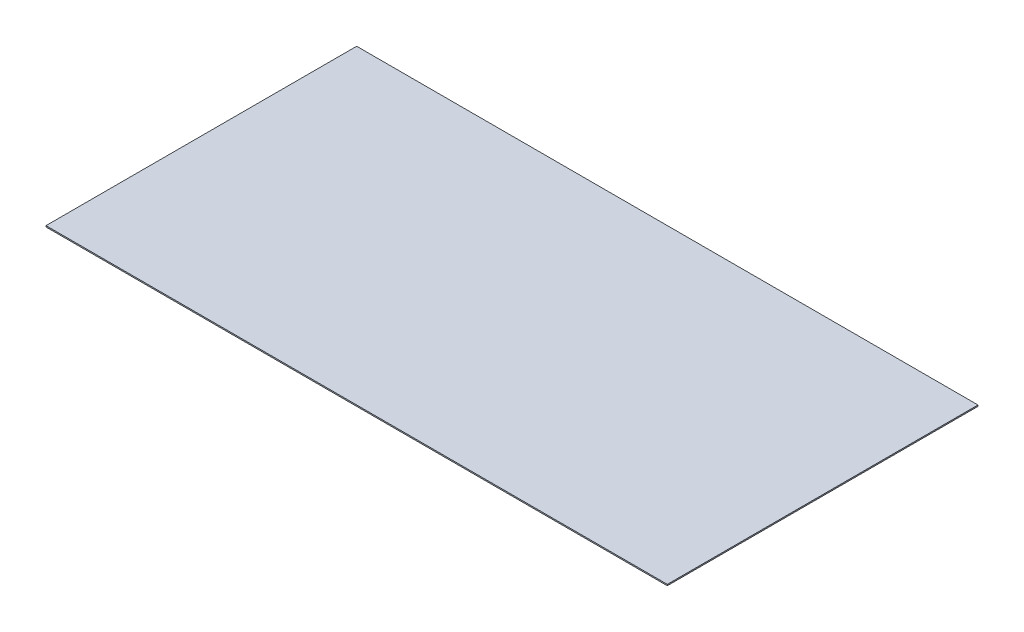
SolidWorks part; units mm, degrees
ref_plane "Front Plane" through (0, 0, 0) normal (0, 0, 1) x (1, 0, 0)
ref_plane "Top Plane" through (0, 0, 0) normal (0, 1, 0) x (1, 0, 0)
ref_plane "Right Plane" through (0, 0, 0) normal (1, 0, 0) x (0, 0, -1)
sketch "Sketch1" plane through (0, 0, 0) normal (0, 1, 0) x (1, 0, 0)
  line L1 (-1000, 500) -> (1000, 500)
  line L2 (-1000, 500) -> (-1000, -500)
  line L3 (-1000, -500) -> (1000, -500)
  line L4 (1000, 500) -> (1000, -500)
  line L5 (-1000, 500) -> (1000, -500) construction
  line L6 (-1000, -500) -> (1000, 500) construction
  point P0 (0, 0)
  dimension "D1" = 1000
  dimension "D2" = 2000
extrude "Boss-Extrude1" add sketch "Sketch1" along normal blind 4
equation "\"D1@Sketch1\"=\"absorber_plate_width\""
equation "\"D2@Sketch1\"=\"absorber_plate_length\""
equation "\"absorber_plate_width\" = 1000mm"
equation "\"absorber_plate_length\" = 2000mm"
equation "\"absorber_plate_thickness\" = 4mm"
equation "\"groove_depth\" = 10mm"
equation "\"frame_thickness\" = 60mm"
equation "\"bend_radius\"= 10mm"
equation "\"insulation_thickness\" = 50mm"
equation "\"D1@Boss-Extrude1\"=\"absorber_plate_thickness\""
